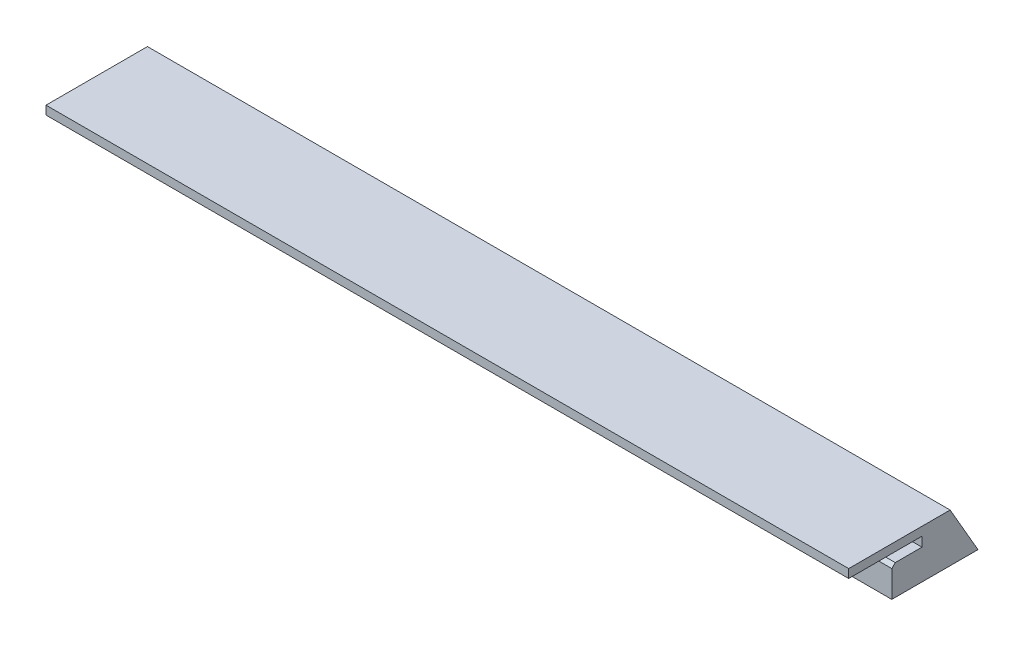
SolidWorks part; units mm, degrees
ref_plane "前视基准面" through (0, 0, 0) normal (0, 0, 1) x (1, 0, 0)
ref_plane "上视基准面" through (0, 0, 0) normal (0, 1, 0) x (1, 0, 0)
ref_plane "右视基准面" through (0, 0, 0) normal (1, 0, 0) x (0, 0, -1)
other "Configuration Table"
sketch "草图2" plane through (0, 0, 0) normal (0, 1, 0) x (1, 0, 0)
  line L1 (0, 0) -> (93.1, 0)
  line L2 (0, 0) -> (0, 10)
  line L3 (0, 10) -> (93.1, 10)
  line L4 (93.1, 0) -> (93.1, 10)
  dimension "D1" = 93.1
  dimension "D2" = 10
extrude "凸台-拉伸1" add sketch "草图2" along normal blind 3.5
sketch "草图4" plane through (0, 3.5, 0) normal (0, 1, 0) x (1, 0, 0)
  line L0 (93.1, 0) -> (93.1, 10) construction
  line L1 (0, 10) -> (93.1, 10)
  line L2 (0, 10) -> (0, 3.5)
  line L3 (0, 3.5) -> (93.1, 3.5)
  line L4 (93.1, 10) -> (93.1, 3.5)
  dimension "D1" = 6.5
extrude "凸台-拉伸2" add sketch "草图4" along normal blind 1.1
sketch "草图5" plane through (0, 4.6, 0) normal (0, 1, 0) x (1, 0, 0)
  line L0 (93.1, 3.5) -> (93.1, 10) construction
  line L1 (0, 10) -> (93.1, 10)
  line L2 (0, 10) -> (0, 0)
  line L3 (0, 0) -> (93.1, 0)
  line L4 (93.1, 10) -> (93.1, 0)
  dimension "D1" = 10
extrude "凸台-拉伸3" add sketch "草图5" along normal blind 2
sketch "草图6" plane through (0, 0, 0) normal (-1, 0, 0) x (0, 0, 1)
  line L0 (-10, 0) -> (-6.1895, 6.6)
  line L1 (-10, 0) -> (0, 0) construction
  line L2 (-10, 6.6) -> (-10, 0) construction
  line L3 (-10, 6.6) -> (0, 6.6) construction
  line L4 (-6.1895, 6.6) -> (-10, 6.6)
  line L5 (-10, 6.6) -> (-10, 0)
  dimension "D1" = 30
extrude "切除-拉伸1" cut sketch "草图6" against normal through all
sketch "草图7" plane through (0, 0, -3.5) normal (0, 0, 1) x (1, 0, 0)
  line L0 (0, 4.6) -> (93.1, 4.6) construction
  line L1 (5, 4.6) -> (88.1, 4.6)
  line L2 (5, 4.6) -> (5, 3.5)
  line L3 (5, 3.5) -> (88.1, 3.5)
  line L4 (88.1, 4.6) -> (88.1, 3.5)
  line L5 (0, 3.5) -> (93.1, 3.5) construction
  line L6 (0, 4.6) -> (0, 3.5) construction
  line L7 (93.1, 4.6) -> (93.1, 3.5) construction
  dimension "D1" = 5
  dimension "D2" = 5
extrude "凸台-拉伸4" add sketch "草图7" along normal up to surface (3.5 mm away) up to face at (46.55, 1.75, 0)
chamfer "倒角1" distance 0.4 angle 45 2 edges at (2.5, 3.5, 0) (90.6, 3.5, 0)
sketch "草图8" plane through (0, 0, 0) normal (0, -1, 0) x (1, 0, 0)
  line L0 (46.55, 147) -> (46.55, 0) construction
  line L1 (0, 0) -> (93.1, 0) construction
  line L2 (5, 0) -> (0, 0) construction
  circle A0 centre (46.55, 147) radius 150
  dimension "D1" = 300
  dimension "D2" = 147
extrude "切除-拉伸2" cut sketch "草图8" against normal up to next
sketch "草图9" plane through (0, 0, 0) normal (0, 0, 1) x (1, 0, 0)
  line L1 (0, 4.6) -> (93.1, 4.6)
  line L2 (0, 4.6) -> (0, 6.6)
  line L3 (0, 6.6) -> (93.1, 6.6)
  line L4 (93.1, 4.6) -> (93.1, 6.6)
extrude "凸台-拉伸5" add sketch "草图9" along normal blind 5 and the other way up to next
sketch "草图10" plane through (93.1, 0, 0) normal (1, 0, 0) x (0, 0, -1)
  line L0 (10, 0) -> (6.1895, 6.6) construction
  line L1 (-5, 6.6) -> (6.7668, 6.6)
  line L2 (-5, 6.6) -> (-5, 5.6)
  line L3 (-5, 5.6) -> (6.7668, 5.6)
  line L4 (6.7668, 6.6) -> (6.7668, 5.6)
  dimension "D1" = 1
extrude "切除-拉伸3" cut sketch "草图10" against normal up to next
